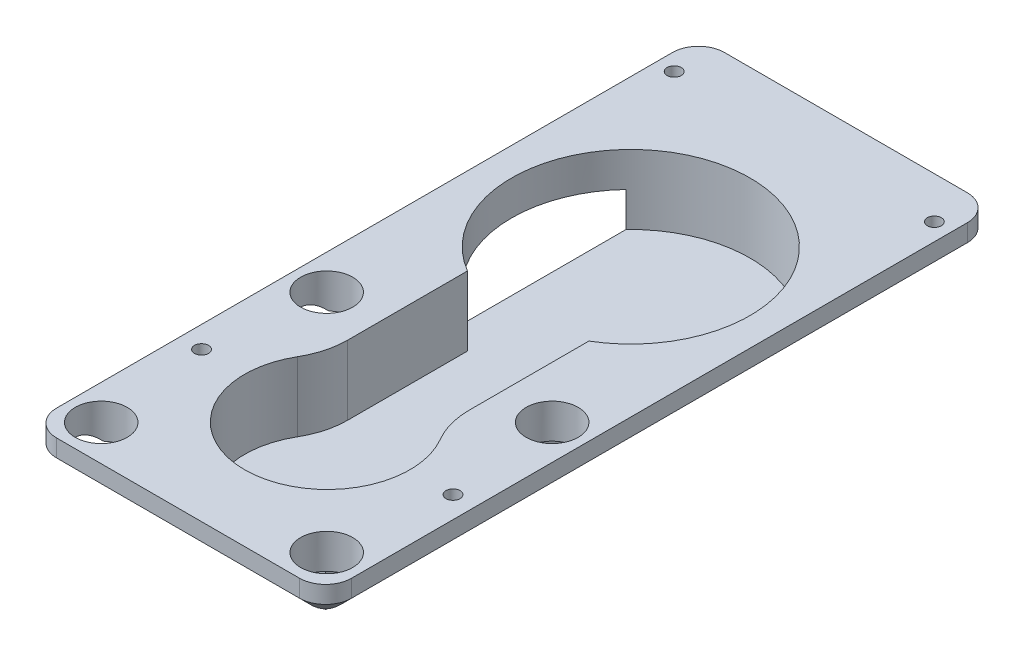
SolidWorks part; units mm, degrees
ref_plane "前视基准面" through (0, 0, 0) normal (0, 0, 1) x (1, 0, 0)
ref_plane "上视基准面" through (0, 0, 0) normal (0, 1, 0) x (1, 0, 0)
ref_plane "右视基准面" through (0, 0, 0) normal (1, 0, 0) x (0, 0, -1)
other "Configuration Table"
sketch "草图1" plane through (0, 0, 0) normal (0, 1, 0) x (1, 0, 0)
  line L0 (0, 0) -> (28, 0)
  line L1 (-3, 77) -> (-3, 3)
  line L2 (31, 77) -> (-3, 77)
  line L3 (31, 3) -> (31, 77)
  arc A0 (28, 0) -> (31, 3) centre (28, 3) ccw
  arc A1 (-3, 3) -> (0, 0) centre (0, 3) ccw
  point P6 (0, 0)
  point P7 (12.8308, 38.262)
  point P9 (0, 0)
  point P11 (0, 0)
  point P12 (0, 0)
  point P13 (0, 0)
  point P14 (-22.5489, 32.9875)
  point P15 (0, 0)
  point P16 (-22.5489, 38.262)
  dimension "D1" = 3
  dimension "D2" = 3
  dimension "D3" = 28
  dimension "D4" = 74
  dimension "D5" = 34
extrude "凸台-拉伸1" add sketch "草图1" along normal blind 12
extrude "切除-拉伸1" cut sketch "草图2" against normal blind 12
sketch "草图2" plane through (14, 12, -382.2) normal (0, 1, 0) x (1, 0, 0)
  circle A4 centre (13, -352.0691) radius 3
  circle A5 centre (-13, -352.0691) radius 3
  circle A6 centre (13, -378.0691) radius 3
  circle A7 centre (-13, -378.0691) radius 3
  circle A12 centre (-15, -310) radius 0.81
  circle A13 centre (15, -310) radius 0.81
  circle A14 centre (14.5, -365) radius 0.81
  circle A15 centre (-14.5, -365) radius 0.81
extrude "切除-拉伸2" cut sketch "草图3" against normal blind 8
sketch "草图3" plane through (14, 12, -382.2) normal (0, 1, 0) x (1, 0, 0)
  line L0 (-7, -341.8348) -> (-7, -355.6399)
  line L1 (7, -355.6399) -> (7, -341.8348)
  arc A10 (-8.2317, -360.1844) -> (-7, -355.6399) centre (-16, -355.6399) ccw
  arc A11 (7, -341.8348) -> (-7, -341.8348) centre (0, -330) ccw
  arc A12 (7, -355.6399) -> (8.2317, -360.1844) centre (16, -355.6399) ccw
  arc A13 (-8.2317, -360.1844) -> (8.2317, -360.1844) centre (0, -365) ccw
  point P15 (-9, -342.9252)
  point P17 (9, -342.9252)
  point P19 (-9.958, -359.5847)
fillet "圆角1" radius 3 2 edges at (-3, 6, -77) (31, 6, -77)
sketch "草图4" plane through (0, 0, 0) normal (0, -1, 0) x (1, 0, 0)
  circle A0 centre (-0.5, -17.2) radius 2.25
  circle A1 centre (28.5, -17.2) radius 2.25
  circle A2 centre (-1, -72.2) radius 2.25
  circle A3 centre (29, -72.2) radius 2.25
  dimension "D1" = 4.5
  dimension "D2" = 4.5
  dimension "D3" = 4.5
  dimension "D4" = 4.5
extrude "切除-拉伸3" cut sketch "草图4" against normal blind 10
sketch "草图5" plane through (0, 0, 0) normal (0, -1, 0) x (1, 0, 0)
  line L0 (28, -77) -> (0, -77) construction
  line L1 (0, 0) -> (28, 0) construction
  line L2 (31, -3) -> (31, -71.1692) construction
  line L3 (-3, -71.1692) -> (-3, -3) construction
  line L4 (28, -77) -> (0, -77)
  line L5 (0, 0) -> (28, 0)
  line L6 (31, -3) -> (31, -71.1692)
  line L7 (-3, -71.1692) -> (-3, -3)
  line L8 (4, -70) -> (4, -7)
  line L9 (4, -7) -> (24, -7)
  line L10 (24, -7) -> (24, -70)
  line L11 (24, -70) -> (4, -70)
  line L12 (0, 0) -> (-3, 0)
  line L13 (-3, 0) -> (-3, -3)
  line L14 (-3, -71.1692) -> (-3, -77)
  line L15 (-3, -77) -> (0, -77)
  line L16 (28, -77) -> (31, -77)
  line L17 (31, -77) -> (31, -71.1692)
  line L18 (28, 0) -> (31, 0)
  line L19 (31, 0) -> (31, -3)
  line L20 (4, -71.1692) -> (4, -3) construction
  line L21 (0, -7) -> (28, -7) construction
  line L22 (24, -3) -> (24, -71.1692) construction
  line L23 (28, -70) -> (0, -70) construction
  dimension "D1" = 20
extrude "切除-拉伸4" cut sketch "草图5" against normal blind 8
chamfer "倒角4" distance 4 angle 40 4 edges at (24, 0, -38.5) (14, 0, -70) (4, 0, -38.5) (14, 0, -7)
chamfer "倒角5" distance 2 angle 45 10 edges at (14, 8, 0) (31, 8, -37.0846) (-3, 8, -73.6154) (31, 8, -73.6154) (-2.1213, 8, -76.1213) (30.1213, 8, -76.1213) (14, 8, -77) (30.1213, 8, -0.8787) (-2.1213, 8, -0.8787) (-3, 8, -37.0846)
